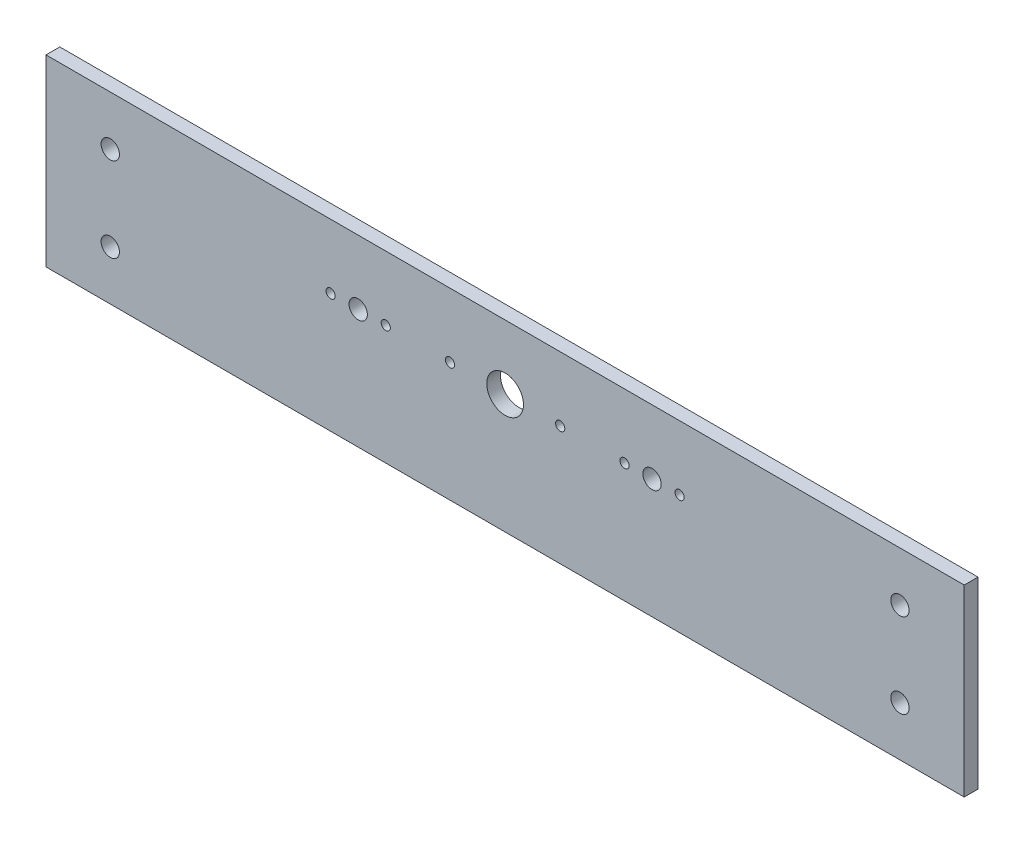
SolidWorks part; units mm, degrees
ref_plane "Front Plane" through (0, 0, 0) normal (0, 0, 1) x (1, 0, 0)
ref_plane "Top Plane" through (0, 0, 0) normal (0, 1, 0) x (1, 0, 0)
ref_plane "Right Plane" through (0, 0, 0) normal (1, 0, 0) x (0, 0, -1)
sketch "Sketch2" plane through (0, 0, 0) normal (0, 0, 1) x (1, 0, 0)
  line L1 (0, 100) -> (500, 100)
  line L2 (0, 100) -> (0, 0)
  line L3 (0, 0) -> (500, 0)
  line L4 (500, 100) -> (500, 0)
  dimension "D1" = 100
  dimension "D2" = 500
extrude "Boss-Extrude1" add sketch "Sketch2" along normal blind 7.5
sketch "Sketch9" plane through (0, 0, 7.5) normal (0, 0, 1) x (1, 0, 0)
  circle A0 centre (170, 65) radius 5
  circle A1 centre (185, 65) radius 2.5
  circle A2 centre (155, 65) radius 2.5
  circle A3 centre (330, 65) radius 5
  circle A4 centre (345, 65) radius 2.5
  circle A5 centre (315, 65) radius 2.5
  circle A6 centre (250, 65) radius 10
  circle A7 centre (280, 65) radius 2.5
  circle A8 centre (220, 65) radius 2.5
extrude "Cut-Extrude3" cut sketch "Sketch9" against normal through all
sketch "Sketch11" plane through (0, 0, 7.5) normal (0, 0, 1) x (1, 0, 0)
  circle A0 centre (35, 73) radius 5
  circle A1 centre (35, 27) radius 5
  circle A2 centre (465, 27) radius 5
  circle A3 centre (465, 73) radius 5
  dimension "D2" = 46
extrude "Cut-Extrude4" cut sketch "Sketch11" against normal through all
